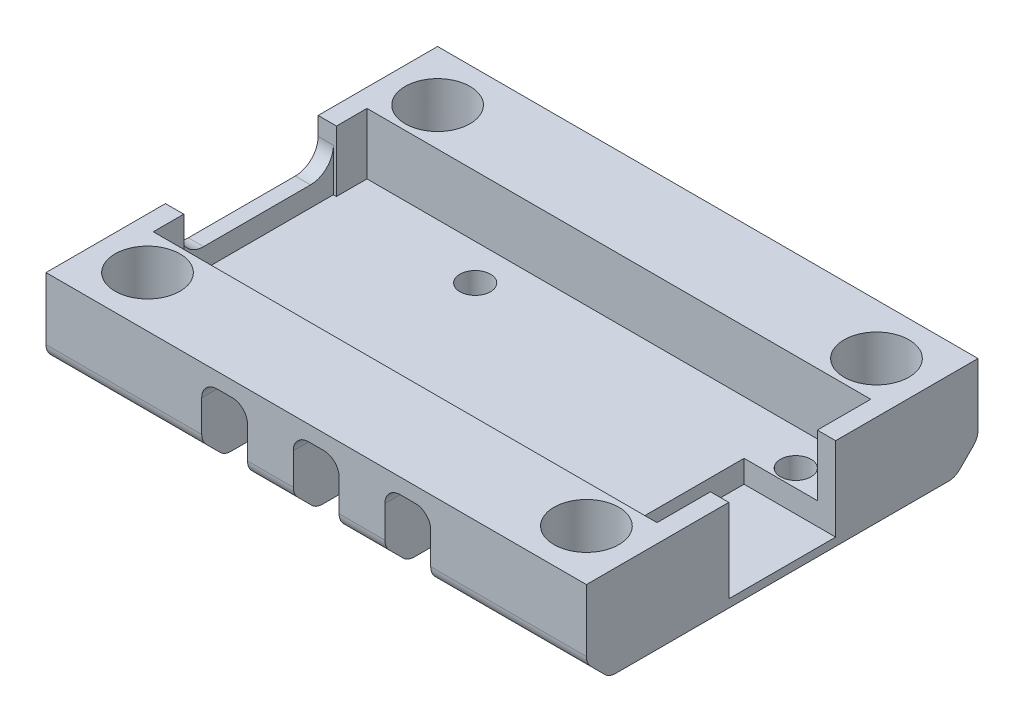
SolidWorks part; units mm, degrees
ref_plane "Front Plane" through (0, 0, 0) normal (0, 0, 1) x (1, 0, 0)
ref_plane "Top Plane" through (0, 0, 0) normal (0, 1, 0) x (1, 0, 0)
ref_plane "Right Plane" through (0, 0, 0) normal (1, 0, 0) x (0, 0, -1)
sketch "Sketch1" plane through (0, 0, 0) normal (0, 1, 0) x (1, 0, 0)
  line L0 (0, 7) -> (33, 7) construction
  line L1 (0, 0) -> (33, 0)
  line L2 (0, 0) -> (0, 14)
  line L3 (0, 14) -> (33, 14)
  line L4 (33, 0) -> (33, 14)
  line L6 (33, 10.5) -> (35, 10.5)
  line L7 (33, 10.5) -> (33, 3.5)
  line L8 (33, 3.5) -> (35, 3.5)
  line L9 (35, 10.5) -> (35, 3.5)
  line L10 (-1.2, -5.825) -> (34.2, -5.825)
  line L11 (-1.2, -5.825) -> (-1.2, 19.825)
  line L12 (-1.2, 19.825) -> (34.2, 19.825)
  line L13 (34.2, -5.825) -> (34.2, 19.825)
  line L14 (-1.2, -5.825) -> (34.2, 19.825) construction
  line L15 (-1.2, 19.825) -> (34.2, -5.825) construction
  line L16 (-1.2, 12) -> (0, 12)
  line L17 (-1.2, 12) -> (-1.2, 2)
  line L18 (-1.2, 2) -> (0, 2)
  line L19 (0, 12) -> (0, 2)
  circle A0 centre (2.125, 16.5) radius 2.125
  circle A1 centre (2.125, -2.5) radius 2.125
  circle A2 centre (30.875, -2.5) radius 2.125
  circle A3 centre (30.875, 16.5) radius 2.125
  point P13 (35, 7)
  point P18 (16.5, 7)
  point P29 (0, 12)
  point P30 (30, 0)
  dimension "D3" = 4.25
  dimension "D7" = 1.2
  dimension "D1" = 33
  dimension "D2" = 14
  dimension "D4" = 7
  dimension "D5" = 2
  dimension "D6" = 19
  dimension "D8" = 1.2
  dimension "D9" = 10
extrude "Boss-Extrude1" add sketch "Sketch1" along normal blind 2 contours L10 L13 L8 L4 L1 L2 L3 L6 L12 L11 A3 A2 A1 A0 | L1 L4 L3 L2 | L8 L13 L6 L4 | L11 L16 L2 L3 L4 L6 L13 L12 A3 A0 | L11 L18 L2 L16 region at (16.5, 0, -7) region at (16.6669, 0, 2.8189) region at (-0.6, 0, -7) region at (33.6, 0, -7) region at (16.6669, 0, -16.8189)
extrude "Boss-Extrude2" add sketch "Sketch1<3>" along normal blind 6 contours L10 L13 L8 L4 L1 L2 L3 L6 L12 L11 A3 A2 A1 A0 | L11 L16 L2 L3 L4 L6 L13 L12 A3 A0 region at (16.6669, 0, 2.8189) region at (16.6669, 0, -16.8189)
sketch "Sketch1<3>" plane through (0, 0, 0) normal (0, 1, 0) x (1, 0, 0) same geometry as "Sketch1"
sketch "Sketch2" plane through (0, 0, 0) normal (0, -1, 0) x (-1, 0, 0)
  line L1 (-9, -1.325) -> (-12, -1.325)
  line L2 (-9, -1.325) -> (-9, -5.825)
  line L3 (-9, -5.825) -> (-12, -5.825)
  line L4 (-12, -1.325) -> (-12, -5.825)
  line L5 (-15, -5.825) -> (-18, -5.825)
  line L6 (-15, -5.825) -> (-15, -1.325)
  line L7 (-15, -1.325) -> (-18, -1.325)
  line L8 (-18, -5.825) -> (-18, -1.325)
  line L9 (-21, -5.825) -> (-24, -5.825)
  line L10 (-21, -5.825) -> (-21, -1.325)
  line L11 (-21, -1.325) -> (-24, -1.325)
  line L12 (-24, -5.825) -> (-24, -1.325)
  line L13 (-21, 15.325) -> (-24, 15.325)
  line L14 (-21, 15.325) -> (-21, 19.825)
  line L15 (-21, 19.825) -> (-24, 19.825)
  line L16 (-24, 15.325) -> (-24, 19.825)
  line L17 (-15, 15.325) -> (-18, 15.325)
  line L18 (-15, 15.325) -> (-15, 19.825)
  line L19 (-15, 19.825) -> (-18, 19.825)
  line L20 (-18, 15.325) -> (-18, 19.825)
  line L21 (-9, 15.325) -> (-12, 15.325)
  line L22 (-9, 15.325) -> (-9, 19.825)
  line L23 (-9, 19.825) -> (-12, 19.825)
  line L24 (-12, 15.325) -> (-12, 19.825)
  line L30 (1.2, 19.825) -> (-34.2, 19.825) construction
  line L34 (1.2, -5.825) -> (-34.2, -5.825) construction
  dimension "D1" = 4.5
extrude "Cut-Extrude1" cut sketch "Sketch2" against normal blind 5
chamfer "Chamfer1" distance 1.5 angle 45 14 edges at (3.9, 0, -19.825) (13.5, 0, -19.825) (29.1, 0, -19.825) (19.5, 0, -19.825) (3.9, 0, 5.825) (29.1, 0, 5.825) (19.5, 0, 5.825) (13.5, 0, 5.825) (10.5, 5, 1.325) (16.5, 5, 1.325) (22.5, 5, 1.325) (22.5, 5, -15.325) (10.5, 5, -15.325) (16.5, 5, -15.325)
fillet "Fillet1" radius 1 44 edges at (21, 1.75, -15.325) (21, 5, -18.325) (15, 5, -18.325) (15, 1.75, -15.325) (9, 1.75, -15.325) (9, 5, -18.325) (12, 1.75, -15.325) (12, 5, -18.325) (24, 5, -18.325) (24, 1.75, -15.325) (18, 1.75, -15.325) (18, 5, -18.325) (21, 5, 4.325) (9, 5, 4.325) (15, 5, 4.325) (24, 5, 4.325) (12, 5, 4.325) (18, 5, 4.325) (12, 1.75, 1.325) (18, 1.75, 1.325) (9, 1.75, 1.325) (15, 1.75, 1.325) (21, 1.75, 1.325) (24, 1.75, 1.325) (33.0818, 0, -18.325) (29.1, 1.5, -19.825) (26.8932, 0, -18.325) (19.5, 1.5, -19.825) (19.5, 0, -18.325) (13.5, 1.5, -19.825) (13.5, 0, -18.325) (-0.0818, 0, -18.325) (3.9, 1.5, -19.825) (6.1068, 0, -18.325) (-0.0818, 0, 4.325) (6.1068, 0, 4.325) (3.9, 1.5, 5.825) (13.5, 1.5, 5.825) (13.5, 0, 4.325) (19.5, 0, 4.325) (33.0818, 0, 4.325) (19.5, 1.5, 5.825) (26.8932, 0, 4.325) (29.1, 1.5, 5.825)
sketch "Sketch3" plane through (34.2, 0, 0) normal (1, 0, 0) x (0, 0, -1)
  line L0 (3.5, 6) -> (10.5, 6)
  line L1 (10.5, 6) -> (10.5, 0.5293)
  line L2 (10.5, 0.5293) -> (3.5, 0.5293)
  line L3 (3.5, 0.5293) -> (3.5, 6)
extrude "Cut-Extrude2" cut sketch "Sketch3" against normal blind 6
sketch "Sketch4" plane through (0, 2, 0) normal (0, 1, 0) x (1, 0, 0)
  circle A0 centre (9.4469, 11.6417) radius 1
  circle A1 centre (30.447, 11.6417) radius 1
  circle A2 centre (30.447, 2.1417) radius 1
  dimension "D1" = 2
extrude "Cut-Extrude3" cut sketch "Sketch4" against normal blind 2
sketch "Sketch5" plane through (-1.2, 0, 0) normal (-1, 0, 0) x (0, 0, 1)
  line L0 (-2, 6) -> (-2, 2) construction
  line L1 (-12, 2) -> (-2, 2)
  line L2 (-12, 2) -> (-12, 3.3103)
  line L3 (-12, 3.3103) -> (-2, 3.3103)
  line L4 (-2, 2) -> (-2, 3.3103)
extrude "Boss-Extrude3" add sketch "Sketch5" against normal blind 1
fillet "Fillet2" radius 1.5 2 edges at (-0.7, 3.3103, -2) (-0.7, 3.3103, -12)
